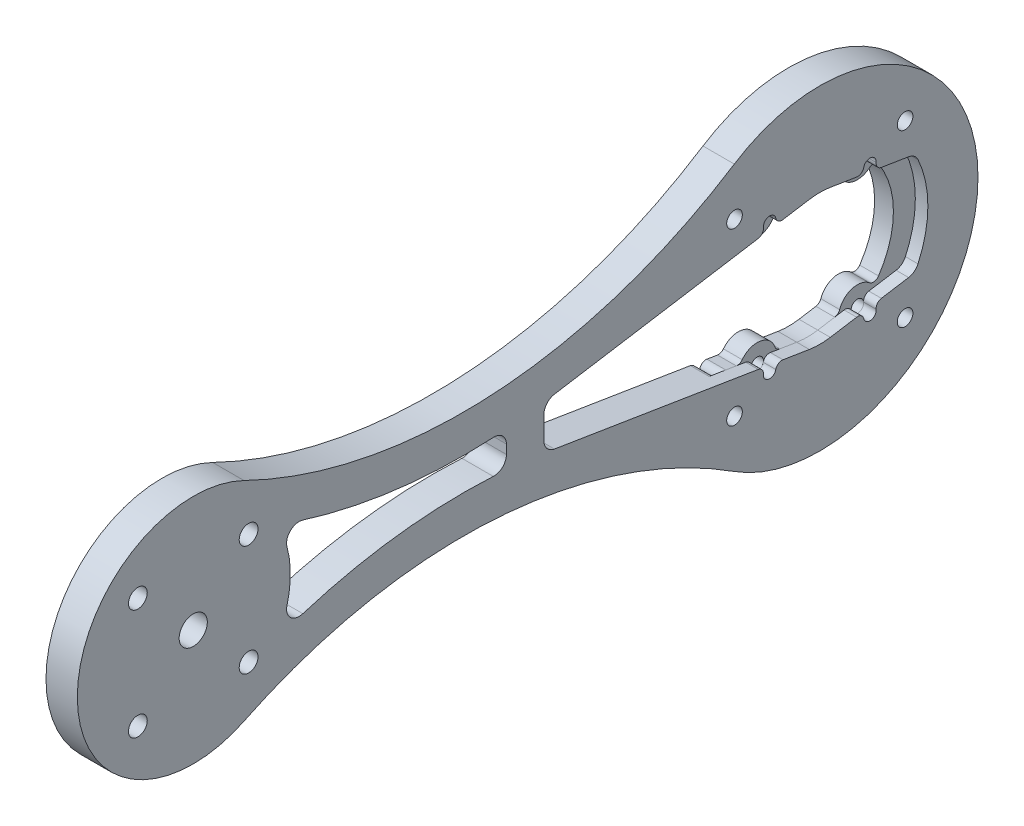
SolidWorks part; units mm, degrees
material "Thornel Mat VMA"
ref_plane "前视基准面" through (0, 0, 0) normal (0, 0, 1) x (1, 0, 0)
ref_plane "上视基准面" through (0, 0, 0) normal (0, 1, 0) x (1, 0, 0)
ref_plane "右视基准面" through (0, 0, 0) normal (1, 0, 0) x (0, 0, -1)
sketch "草图1" plane through (0, 0, 0) normal (1, 0, 0) x (0, 0, -1)
  line L0 (2.75, 0) -> (-2.75, 0) construction
  circle A0 centre (0, 0) radius 19.25 construction
  circle A1 centre (-100, 0) radius 12.5 construction
  arc A2 (-13.645, -21.2456) -> (-13.645, 21.2456) centre (0, 0) ccw
  circle A3 centre (13.6118, 13.6118) radius 1.25
  circle A4 centre (-108.8388, 8.8388) radius 1.5
  circle A5 centre (13.6118, -13.6118) radius 1.25
  circle A6 centre (-13.6118, -13.6118) radius 1.25
  circle A7 centre (-13.6118, 13.6118) radius 1.25
  circle A8 centre (-91.1612, 8.8388) radius 1.5
  circle A9 centre (-91.1612, -8.8388) radius 1.5
  circle A10 centre (-108.8388, -8.8388) radius 1.5
  arc A11 (-91.9007, 16.6328) -> (-91.9007, -16.6328) centre (-100, 0) ccw
  arc A12 (-91.9007, 16.6328) -> (-13.645, 21.2456) centre (-56.8766, 88.5586) ccw
  arc A13 (-91.9007, -16.6328) -> (-13.645, -21.2456) centre (-56.8766, -88.5586) cw
  circle A14 centre (-100, 0) radius 2.25
  circle A15 centre (0, 0) radius 10.5
  point P19 (0, 0)
  point P26 (-100, 0)
  dimension "D1" = 100
  dimension "D2" = 38.5
  dimension "D3" = 25
  dimension "D4" = 4
  dimension "D5" = 2.5
  dimension "D6" = 4
  dimension "D7" = 3
  dimension "D8" = 6
  dimension "D9" = 6
  dimension "D10" = 80
  dimension "D11" = 4.5
  dimension "D12" = 21
extrude "凸台-拉伸1" add sketch "草图1" along normal blind 5
sketch "草图2" plane through (5, 0, 0) normal (1, 0, 0) x (0, 0, -1)
  line L0 (-43.1528, 3.6606) -> (-1.6756, 10.3654)
  line L1 (2.75, 0) -> (-2.75, 0) construction
  line L2 (-43.1528, -3.6606) -> (-1.6756, -10.3654)
  line L3 (0, 2.75) -> (0, -2.75) construction
  line L4 (15.1864, -8.1814) -> (1.6756, -10.3654)
  line L5 (15.1864, 8.1814) -> (1.6756, 10.3654)
  arc A0 (-50.08, -2.8275) -> (-50.08, 2.8275) centre (-100, 0) ccw
  arc A1 (-44.1102, -3.5114) -> (-44.1102, 3.5114) centre (-100, 0) ccw
  circle A6 centre (0, 0) radius 10.5 construction
  arc A7 (-1.6756, 10.3654) -> (-1.6756, -10.3654) centre (0, 0) ccw
  arc A8 (-86.6508, -7.8771) -> (-86.6508, 7.8771) centre (-100, 0) ccw
  arc A9 (-94.5275, 11.2384) -> (-94.5275, -11.2384) centre (-100, 0) ccw
  arc A10 (-10.4026, -16.1972) -> (-94.5275, -11.2384) centre (-56.8766, -88.5586) ccw
  arc A11 (-94.5275, 11.2384) -> (-10.4026, 16.1972) centre (-56.8766, 88.5586) ccw
  arc A13 (-43.1528, -3.6606) -> (-86.6508, -7.8771) centre (-56.8766, -88.5586) ccw
  arc A14 (-86.6508, 7.8771) -> (-43.1528, 3.6606) centre (-56.8766, 88.5586) ccw
  arc A15 (-91.9007, 16.6328) -> (-91.9007, -16.6328) centre (-100, 0) ccw construction
  arc A16 (1.6756, 10.3654) -> (1.6756, -10.3654) centre (0, 0) cw
  arc A20 (15.1864, 8.1814) -> (15.1864, -8.1814) centre (0, 0) cw
  arc A21 (-13.645, -21.2456) -> (-13.645, 21.2456) centre (0, 0) ccw construction
  circle M18 centre (0, 0) radius 10.5
  dimension "D2" = 3
  dimension "D3" = 8
  dimension "D4" = 6
  dimension "D5" = 50
  dimension "D1" = 6
extrude "切除-拉伸1" cut sketch "草图2" against normal blind 10 contours A1 L2 L0 M18 | A20 L5 L4 M18 | A14 A8 A13 A0 region at (5, 0, 23.6719) region at (5, 0, -12.3403) region at (5, 0, 70.9949)
fillet "圆角1" radius 2 8 edges at (2.5, -7.8771, 86.6508) (2.5, 8.1814, -15.1864) (2.5, -8.1814, -15.1864) (2.5, 7.8771, 86.6508) (2.5, 2.8275, 50.08) (2.5, -2.8275, 50.08) (2.5, 3.5114, 44.1102) (2.5, -3.5114, 44.1102)
sketch "草图3" plane through (5, 0, 0) normal (1, 0, 0) x (0, 0, -1)
  line L0 (2.75, 0) -> (-2.75, 0) construction
  line L1 (0, 2.75) -> (0, -2.75) construction
  circle A0 centre (-8, 10.25) radius 1
  circle A1 centre (-8, -10.25) radius 1
  circle A2 centre (8, -10.25) radius 1
  circle A3 centre (8, 10.25) radius 1
  dimension "D1" = 2
  dimension "D2" = 20.5
  dimension "D3" = 16
extrude "切除-拉伸2" cut sketch "草图3" against normal blind 10
fillet "圆角2" radius 1 8 edges at (2.5, 9.4373, -7.4173) (2.5, 9.4373, 7.4173) (2.5, -9.2951, 8.2969) (2.5, -9.4373, 7.4173) (2.5, -9.4373, -7.4173) (2.5, -9.2951, -8.2969) (2.5, 9.2951, -8.2969) (2.5, 9.2951, 8.2969)
sketch "草图4" plane through (0, 0, 0) normal (1, 0, 0) x (0, 0, -1)
  arc A0 (-6.3632, 16.0335) -> (-6.3632, -16.0335) centre (0, 0) ccw
  arc A1 (-2.506, 17.067) -> (-6.3632, 16.0335) centre (-4.4646, 16.6622) ccw
  arc A2 (6.3632, 16.0335) -> (2.506, 17.067) centre (4.4646, 16.6622) ccw
  circle A3 centre (12.1976, 12.1976) radius 2 construction
  circle A4 centre (16.6622, 4.4646) radius 2 construction
  circle A5 centre (16.6622, -4.4646) radius 2 construction
  circle A6 centre (12.1976, -12.1976) radius 2 construction
  arc A7 (2.506, -17.067) -> (6.3632, -16.0335) centre (4.4646, -16.6622) ccw
  arc A8 (-6.3632, -16.0335) -> (-2.506, -17.067) centre (-4.4646, -16.6622) ccw
  circle A9 centre (-12.1976, -12.1976) radius 2 construction
  circle A10 centre (-16.6622, -4.4646) radius 2 construction
  circle A11 centre (-16.6622, 4.4646) radius 2 construction
  circle A12 centre (-12.1976, 12.1976) radius 2 construction
  arc A13 (2.506, 17.067) -> (-2.506, 17.067) centre (0, 0) ccw
  arc A14 (-2.506, -17.067) -> (2.506, -17.067) centre (0, 0) ccw
  arc A15 (6.3632, -16.0335) -> (6.3632, 16.0335) centre (0, 0) ccw
  point P5 (23.4141, -7.3463)
  point P6 (0, 0)
  point P29 (0, 0)
  point P30 (0, 0)
  dimension "D1" = 34.5
  dimension "D2" = 4
  dimension "D3" = 12
  dimension "D4" = 4
extrude "切除-拉伸4" cut sketch "草图4" along normal blind 3 from surface starting at face at (0, 0, 3.9976)
extrude "凸台-拉伸2" add sketch "草图4<2>" along normal blind 3 separate body
sketch "草图4<2>" plane through (0, 0, 0) normal (1, 0, 0) x (0, 0, -1) same geometry as "草图4"
sketch "草图5" plane through (3, 0, 0) normal (1, 0, 0) x (0, 0, -1)
  line L0 (-42.3476, 3.7908) -> (-9.8288, 9.0475) construction
  line L1 (14.1748, 8.3449) -> (9.8288, 9.0475) construction
  line L2 (5.8855, 9.6849) -> (1.6756, 10.3654) construction
  line L3 (-5.8855, 9.6849) -> (-1.6756, 10.3654) construction
  line L4 (-42.3476, 3.7908) -> (-10.6837, 8.9093)
  line L5 (14.1748, 8.3449) -> (10.4395, 8.9488)
  line L6 (5.0305, 9.8231) -> (1.6756, 10.3654)
  line L7 (-5.0305, 9.8231) -> (-1.6756, 10.3654)
  line L8 (2.75, 0) -> (-2.75, 0) construction
  line L11 (14.1748, -8.3449) -> (9.8288, -9.0475)
  line L12 (-42.3476, -3.7908) -> (-10.6837, -8.9093)
  line L13 (-42.3476, 3.7908) -> (-42.3476, -3.7908)
  line L14 (-5.0305, -9.8231) -> (-1.6756, -10.3654)
  line L15 (5.0305, -9.8231) -> (1.6756, -10.3654)
  arc A0 (15.6728, -7.2061) -> (15.6728, 7.2061) centre (0, 0) ccw construction
  arc A1 (15.6728, 7.2061) -> (14.1748, 8.3449) centre (13.8556, 6.3706) ccw construction
  arc A3 (8.9942, 10.1423) -> (7.0225, 10.461) centre (8, 10.25) ccw construction
  arc A5 (1.6756, 10.3654) -> (-1.6756, 10.3654) centre (0, 0) ccw construction
  arc A7 (-7.0225, 10.461) -> (-8.9942, 10.1423) centre (-8, 10.25) ccw construction
  arc A9 (15.6728, -7.2061) -> (15.6728, 7.2061) centre (0, 0) ccw
  arc A10 (15.6728, 7.2061) -> (14.1748, 8.3449) centre (13.8556, 6.3706) ccw
  circle A12 centre (8, 10.25) radius 1
  arc A14 (1.6756, 10.3654) -> (-1.6756, 10.3654) centre (0, 0) ccw
  circle A16 centre (-8, 10.25) radius 1
  arc A25 (15.6728, -7.2061) -> (14.1748, -8.3449) centre (13.8556, -6.3706) cw
  arc A26 (10.4395, -8.9488) -> (10.4395, 8.9488) centre (0, 0) ccw
  arc A27 (-10.6837, 8.9093) -> (-5.0305, 9.8231) centre (-8, 10.25) ccw
  arc A28 (5.0305, 9.8231) -> (10.6837, 8.9093) centre (8, 10.25) ccw
  arc A29 (5.0305, -9.8231) -> (10.6837, -8.9093) centre (8, -10.25) cw
  arc A30 (-10.6837, -8.9093) -> (-5.0305, -9.8231) centre (-8, -10.25) cw
  circle A31 centre (-8, -10.25) radius 1
  arc A32 (1.6756, -10.3654) -> (-1.6756, -10.3654) centre (0, 0) cw
  circle A33 centre (8, -10.25) radius 1
  point P49 (7.0864, 10.6566)
  arc M3 (-6.3632, 16.0335) -> (-6.3632, -16.0335) centre (0, 0) ccw
  dimension "D1" = 3.5
  dimension "D2" = 6
extrude "切除-拉伸5" cut sketch "草图5" against normal blind 3 contours L11 A26 L5 A12 L6 A14 L7 A16 L4 L12 M3 | A31 | A33 | A12 | A16 region at (3, 0, 1.7877) region at (3, 10.25, -8) region at (3, 10.25, 8) region at (3, -10.25, 8) region at (3, -10.25, -8)
fillet "圆角3" radius 1 10 edges at (1.5, -16.0335, -6.3632) (1.5, -17.067, -2.506) (1.5, -17.067, 2.506) (1.5, -16.0335, 6.3632) (1.5, -8.1814, 15.1864) (1.5, 8.1814, 15.1864) (1.5, 16.0335, 6.3632) (1.5, 17.067, 2.506) (1.5, 17.067, -2.506) (1.5, 16.0335, -6.3632)
fillet "圆角4" radius 1 18 edges at (1.5, -16.0335, 6.3632) (1.5, -17.067, 2.506) (1.5, -17.067, -2.506) (1.5, -16.0335, -6.3632) (1.5, 16.0335, -6.3632) (1.5, 17.067, -2.506) (1.5, 17.067, 2.506) (1.5, 16.0335, 6.3632) (1.5, -8.1814, 15.1864) (1.5, 8.1814, 15.1864) (1.5, 9.8231, 5.0305) (1.5, 9.8231, -5.0305) (1.5, 8.7561, -10.6016) (1.5, -8.7561, -10.6016) (1.5, -9.8231, -5.0305) (1.5, -9.8231, 5.0305) (1.5, -8.9093, 10.6837) (1.5, 8.9093, 10.6837)
